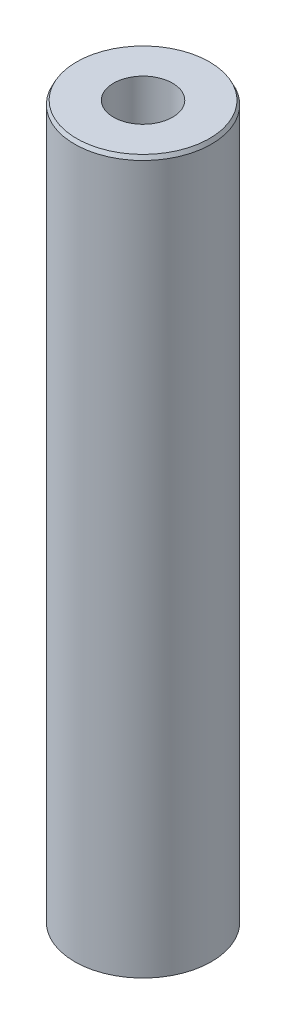
SolidWorks part; units mm, degrees
ref_plane "Front Plane" through (0, 0, 0) normal (0, 0, 1) x (1, 0, 0)
ref_plane "Top Plane" through (0, 0, 0) normal (0, 1, 0) x (1, 0, 0)
ref_plane "Right Plane" through (0, 0, 0) normal (1, 0, 0) x (0, 0, -1)
sketch "Sketch1" plane through (0, 0, 0) normal (0, 1, 0) x (1, 0, 0)
  circle A0 centre (0, 0) radius 57.5
  dimension "SHAFT_OD" = 115
extrude "Boss-Extrude1" add sketch "Sketch1" along normal blind 600
sketch "Sketch2" plane through (0, 0, 0) normal (0, 1, 0) x (1, 0, 0)
  circle A0 centre (0, 0) radius 24.8235
  dimension "BORE_D" = 49.6471
extrude "Cut-Extrude1" cut sketch "Sketch2" along normal through all
chamfer "Chamfer1" distance 3.272 angle 26.9 2 edges at (0, 600, 57.5) (0, 0, 57.5) first distance on face at (0, 600, 57.5) first distance on face at (0, 0, 24.8235)
